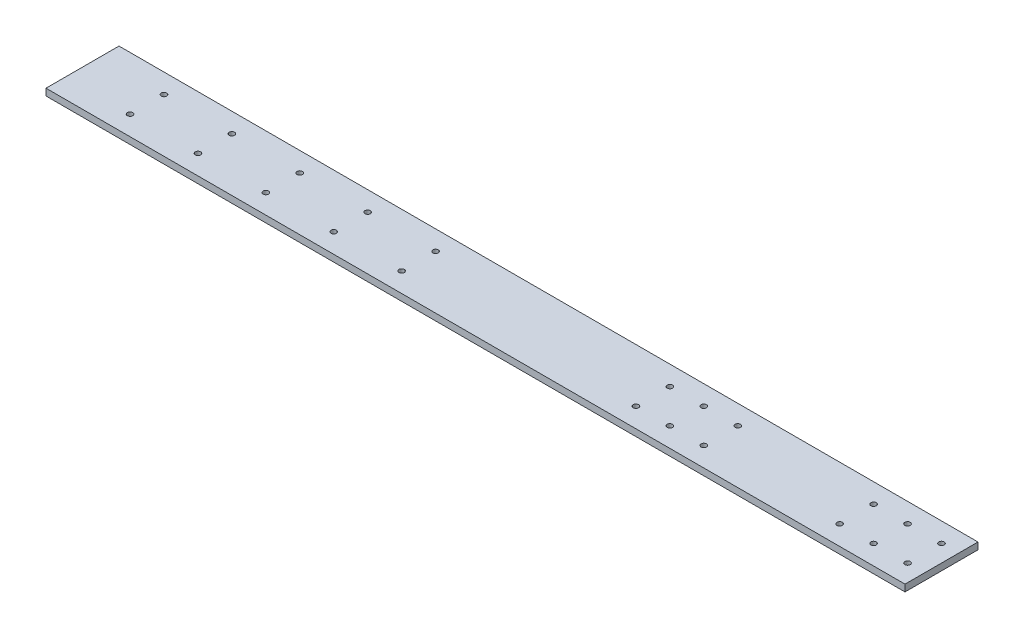
SolidWorks part; units mm, degrees
ref_plane "Front Plane" through (0, 0, 0) normal (0, 0, 1) x (1, 0, 0)
ref_plane "Top Plane" through (0, 0, 0) normal (0, 1, 0) x (1, 0, 0)
ref_plane "Right Plane" through (0, 0, 0) normal (1, 0, 0) x (0, 0, -1)
sketch "Sketch1" plane through (0, 0, 0) normal (0, 1, 0) x (1, 0, 0)
  line L0 (-253, 0) -> (-17, 0) construction
  line L1 (-253, -21.5) -> (253, -21.5)
  line L2 (-253, -21.5) -> (-253, 21.5)
  line L3 (-253, 21.5) -> (253, 21.5)
  line L4 (253, -21.5) -> (253, 21.5)
  line L5 (-253, -21.5) -> (253, 21.5) construction
  line L6 (-253, 21.5) -> (253, -21.5) construction
  line L7 (-17, -35) -> (-17, 35) construction
  line L8 (-17, 21.5) -> (-17, -21.5) construction
  circle A0 centre (-215, 10) radius 1.6
  circle A2 centre (-175, 10) radius 1.6
  circle A3 centre (-135, 10) radius 1.6
  circle A4 centre (-95, 10) radius 1.6
  circle A5 centre (-55, 10) radius 1.6
  circle A8 centre (-175, -10) radius 1.6
  circle A9 centre (-135, -10) radius 1.6
  circle A10 centre (-95, -10) radius 1.6
  circle A11 centre (-55, -10) radius 1.6
  circle A14 centre (-215, -10) radius 1.6
  circle A15 centre (223, 10) radius 1.6
  circle A16 centre (103, 10) radius 1.6
  circle A17 centre (103, -10) radius 1.6
  circle A18 centre (223, -10) radius 1.6
  circle A19 centre (123, -10) radius 1.6
  circle A20 centre (123, 10) radius 1.6
  circle A21 centre (243, 10) radius 1.6
  circle A22 centre (243, -10) radius 1.6
  circle A23 centre (83, -10) radius 1.6
  circle A24 centre (83, 10) radius 1.6
  circle A25 centre (203, 10) radius 1.6
  circle A26 centre (203, -10) radius 1.6
  point P0 (0, 0)
  dimension "D4" = 3.2
  dimension "D5" = 5
  dimension "D1" = 506
  dimension "D2" = 43
  dimension "D3" = 10
  dimension "D7" = 38
  dimension "D8" = 30
  dimension "D9" = 240
  dimension "D6" = 2
  dimension "D10" = 2
  dimension "D11" = 2
  dimension "D12" = 2
  dimension "D13" = 2
extrude "Boss-Extrude1" add sketch "Sketch1" along normal blind 4
